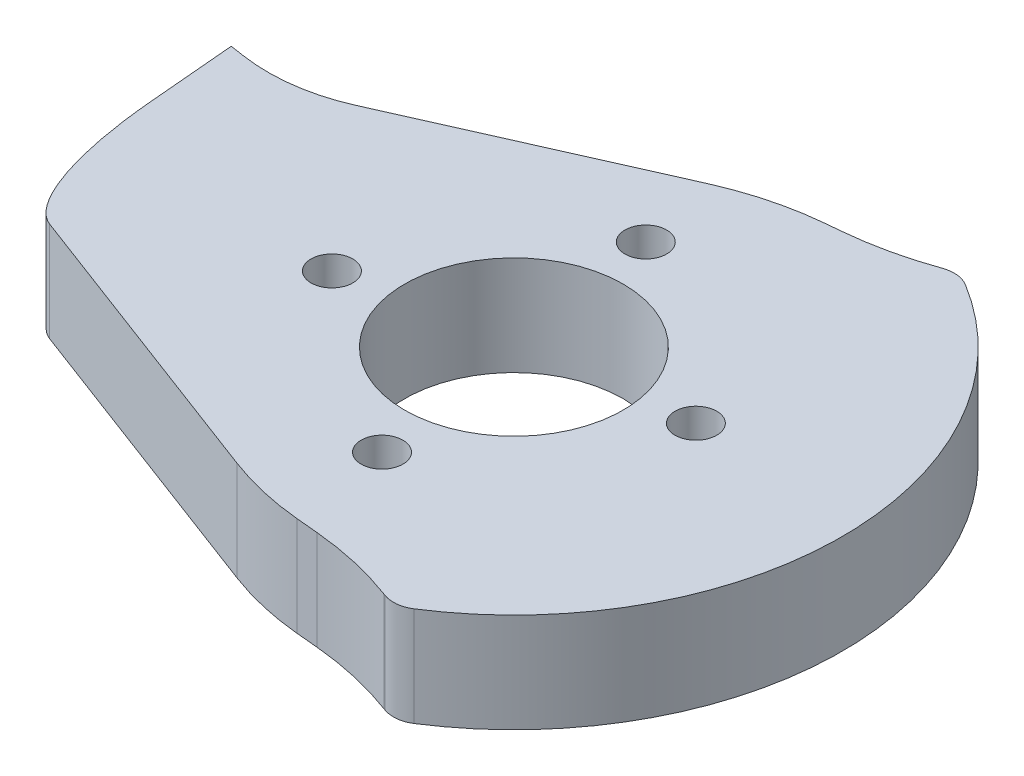
SolidWorks part; units mm, degrees
material "Plain Carbon Steel"
ref_plane "Front Plane" through (0, 0, 0) normal (0, 0, 1) x (1, 0, 0)
ref_plane "Top Plane" through (0, 0, 0) normal (0, 1, 0) x (1, 0, 0)
ref_plane "Right Plane" through (0, 0, 0) normal (1, 0, 0) x (0, 0, -1)
sketch "Sketch1" plane through (0, 0, 0) normal (0, 1, 0) x (1, 0, 0)
  line L5 (-43.8379, 11.61) -> (-37.1995, 10.61)
  line L6 (-37.1995, 10.61) -> (-3.38, 25.61)
  line L7 (12.62, 28.5289) -> (7.3959, 26.61)
  line L8 (7.3959, 26.61) -> (-3.38, 25.61)
  line L11 (-3.38, -25.89) -> (7.3959, -26.89)
  line L12 (7.3959, -26.89) -> (13.12, -29.0266)
  line L13 (-43.8379, 11.61) -> (-41.8379, -11.39)
  line L14 (-41.8379, -11.39) -> (-3.38, -25.89)
  circle A3 centre (-3.38, -0.39) radius 11
  arc A5 (12.62, 28.5289) -> (13.12, -29.0266) centre (-3.38, -0.39) cw
  dimension "D1" = 33.05
  dimension "D2" = 16
  dimension "D8" = 22
  dimension "D10" = 26
  dimension "D7" = 12
  dimension "D3" = 3.38
  dimension "D4" = 0.39
  dimension "D5" = 16.5
  dimension "D6" = 42.2
  dimension "D9" = 11
  dimension "D11" = 1
  dimension "D12" = 25.5
  dimension "D13" = 2
  dimension "D14" = 1
  dimension "D15" = 6.6384
  dimension "D16" = 11
extrude "Boss-Extrude1" add sketch "Sketch1" along normal blind 10
sketch "Sketch2" plane through (0, 10, 0) normal (0, 1, 0) x (1, 0, 0)
  circle A0 centre (12.42, 2.1319) radius 2.1
  circle A2 centre (-0.8581, -16.19) radius 2.1
  circle A3 centre (-19.18, -2.9119) radius 2.1
  circle A4 centre (-5.9019, 15.41) radius 2.1
  circle A6 centre (-3.38, -0.39) radius 11 construction
  point P4 (-2.393, -1.612)
  point P5 (0, 0)
  point P6 (0, 0)
  point P13 (0, 0)
  point P17 (-3.38, -0.39)
  dimension "D2" = 4.2
  dimension "D1" = 16
  dimension "D4" = 0
  dimension "D6" = 15.8
  dimension "D3" = 4
extrude "Cut-Extrude1" cut sketch "Sketch2" against normal blind 10
fillet "Fillet1" radius 18 1 edges at (-41.8379, 5, 11.39) second distance 12 first distance on face at (-42.8379, 5, -0.11)
fillet "Fillet2" radius 18 1 edges at (-37.1995, 5, -10.61)
fillet "Fillet3" radius 30 2 edges at (-3.38, 5, 25.89) (-3.38, 5, -25.61)
fillet "Fillet4" radius 34 2 edges at (7.3959, 5, -26.61) (7.3959, 5, 26.89)
fillet "Fillet7" radius 3 2 edges at (12.62, 5, -28.5289) (13.12, 5, 29.0266)
